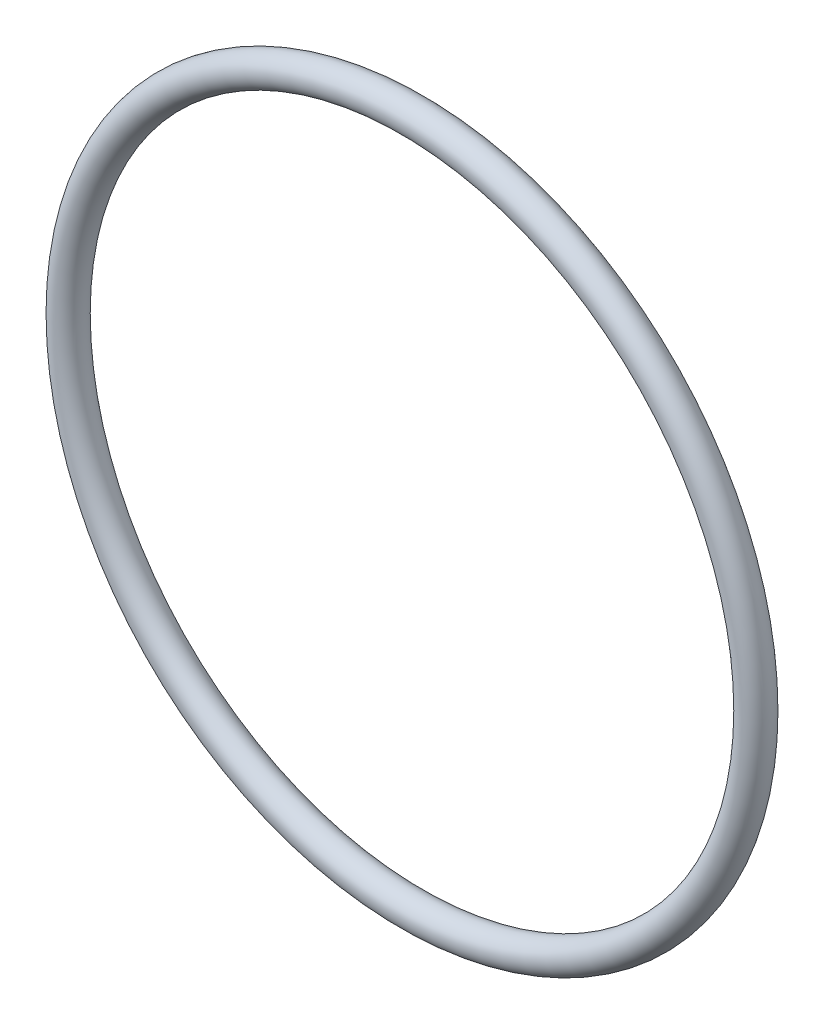
SolidWorks part; units mm, degrees
material "Borracha"
ref_plane "Plano frontal" through (0, 0, 0) normal (0, 0, 1) x (1, 0, 0)
ref_plane "Plano superior" through (0, 0, 0) normal (0, 1, 0) x (1, 0, 0)
ref_plane "Plano direito" through (0, 0, 0) normal (1, 0, 0) x (0, 0, -1)
ref_plane "Plano1" through (0, -32.5, 0) normal (0, 1, 0) x (1, 0, 0)
ref_plane "Plano2" through (0, 0, 1.5) normal (0, 0, 1) x (1, 0, 0)
ref_axis "Eixo1" through (0, -32.5, -88.99) along (0, 0, 1)
sketch "Esboço2" plane through (0, 0, 0) normal (1, 0, 0) x (0, 0, -1)
  line L1 (88.99, -32.5) -> (-88.99, -32.5) construction
  circle A0 centre (0, 0.5) radius 1.5
  dimension "D1" = 31.5
  dimension "D2" = 3
revolve "Revolução1" add sketch "Esboço2" angle 360 about axis through (0, -32.5, -88.99) along (0, 0, 1)
